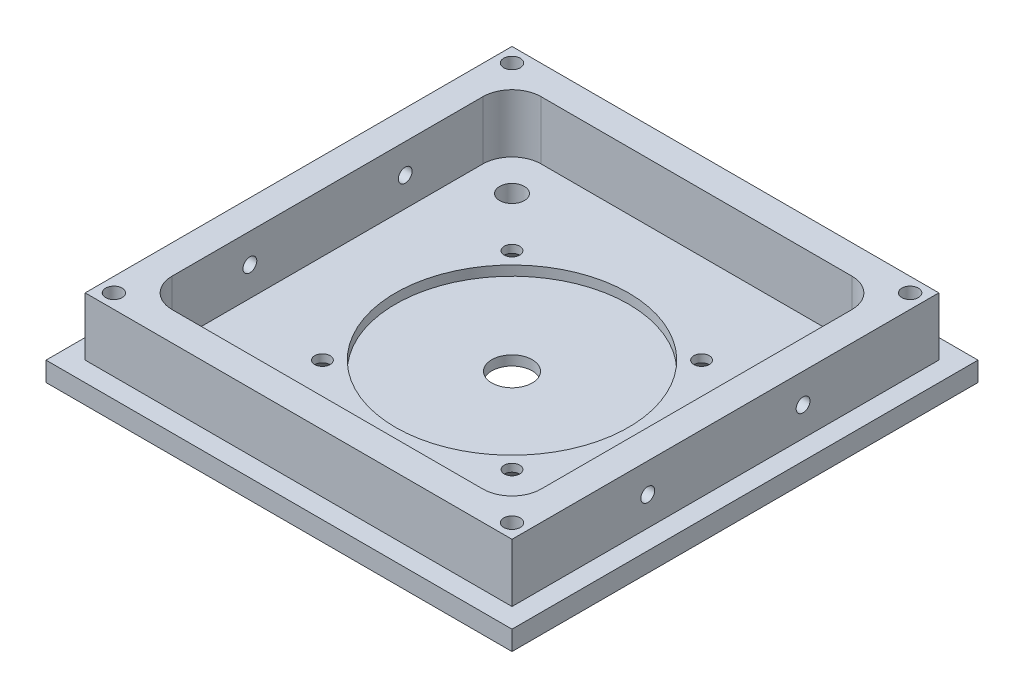
SolidWorks part; units mm, degrees
material "6061-T6 (SS)"
ref_plane "Front Plane" through (0, 0, 0) normal (0, 0, 1) x (1, 0, 0)
ref_plane "Top Plane" through (0, 0, 0) normal (0, 1, 0) x (1, 0, 0)
ref_plane "Right Plane" through (0, 0, 0) normal (1, 0, 0) x (0, 0, -1)
sketch "Sketch1" plane through (0, 0, 0) normal (0, 1, 0) x (1, 0, 0)
  line L1 (-38.1, -38.1) -> (38.1, -38.1)
  line L2 (-38.1, -38.1) -> (-38.1, 38.1)
  line L3 (-38.1, 38.1) -> (38.1, 38.1)
  line L4 (38.1, -38.1) -> (38.1, 38.1)
  line L5 (-38.1, -38.1) -> (38.1, 38.1) construction
  line L6 (-38.1, 38.1) -> (38.1, -38.1) construction
  point P0 (0, 0)
  dimension "D1" = 76.2
  dimension "D2" = 76.2
extrude "Boss-Extrude1" add sketch "Sketch1" along normal blind 3.175
sketch "Sketch2" plane through (0, 3.175, 0) normal (0, 1, 0) x (1, 0, 0)
  line L0 (-38.1, 38.1) -> (-38.1, -38.1) construction
  line L1 (34.8971, -34.8971) -> (-34.8971, -34.8971)
  line L2 (34.8971, -34.8971) -> (34.8971, 34.8971)
  line L3 (34.8971, 34.8971) -> (-34.8971, 34.8971)
  line L4 (-34.8971, -34.8971) -> (-34.8971, 34.8971)
  line L5 (34.8971, -34.8971) -> (-34.8971, 34.8971) construction
  line L6 (34.8971, 34.8971) -> (-34.8971, -34.8971) construction
  line L7 (30.1625, -30.1625) -> (-30.1625, -30.1625)
  line L8 (30.1625, -30.1625) -> (30.1625, 30.1625)
  line L9 (30.1625, 30.1625) -> (-30.1625, 30.1625)
  line L10 (-30.1625, -30.1625) -> (-30.1625, 30.1625)
  line L11 (30.1625, -30.1625) -> (-30.1625, 30.1625) construction
  line L12 (30.1625, 30.1625) -> (-30.1625, -30.1625) construction
  line L14 (38.1, 38.1) -> (-38.1, 38.1) construction
  point P0 (0, 0)
  point P6 (0, 0)
  dimension "D1" = 3.2029
  dimension "D2" = 3.2029
  dimension "D3" = 60.325
extrude "Boss-Extrude2" add sketch "Sketch2" along normal blind 9.525
fillet "Fillet1" radius 4.7625 4 edges at (-30.1625, 7.9375, 30.1625) (30.1625, 7.9375, 30.1625) (30.1625, 7.9375, -30.1625) (-30.1625, 7.9375, -30.1625)
sketch "Sketch3" plane through (0, 3.175, 0) normal (0, 1, 0) x (1, 0, 0)
  circle A0 centre (0, 0) radius 19.05
  dimension "D1" = 38.1
extrude "Cut-Extrude1" cut sketch "Sketch3" against normal blind 1.5875
sketch "Sketch4" plane through (0, 1.5875, 0) normal (0, 1, 0) x (1, 0, 0)
  circle A0 centre (0, 0) radius 3.302
  dimension "D1" = 6.604
extrude "Cut-Extrude2" cut sketch "Sketch4" against normal through all
sketch "Sketch5" plane through (0, 3.175, 0) normal (0, 1, 0) x (1, 0, 0)
  line L1 (15.5, -15.5) -> (-15.5, -15.5)
  line L2 (15.5, -15.5) -> (15.5, 15.5)
  line L3 (15.5, 15.5) -> (-15.5, 15.5)
  line L4 (-15.5, -15.5) -> (-15.5, 15.5)
  line L5 (15.5, -15.5) -> (-15.5, 15.5) construction
  line L6 (15.5, 15.5) -> (-15.5, -15.5) construction
  line L7 (23.5966, -23.5966) -> (-23.5966, -23.5966)
  line L8 (23.5966, -23.5966) -> (23.5966, 23.5966)
  line L9 (23.5966, 23.5966) -> (-23.5966, 23.5966)
  line L10 (-23.5966, -23.5966) -> (-23.5966, 23.5966)
  line L11 (23.5966, -23.5966) -> (-23.5966, 23.5966) construction
  line L12 (23.5966, 23.5966) -> (-23.5966, -23.5966) construction
  circle A0 centre (-15.5, 15.5) radius 1.2637
  circle A1 centre (15.5, 15.5) radius 1.2637
  circle A2 centre (15.5, -15.5) radius 1.2637
  circle A3 centre (-15.5, -15.5) radius 1.2637
  point P2 (0, 0)
  point P10 (0, 0)
  dimension "D2" = 2.5273
  dimension "D1" = 31
  dimension "D3" = 47.1932
hole_wizard "#39 (0.0995) Diameter Hole1" positions "Sketch7" profile "Sketch6" hole size "#39" standard "ANSI Inch" end condition through all
sketch "Sketch7" plane through (0, 3.175, 0) normal (0, 1, 0) x (1, 0, 0)
  point P0 (15.5, 15.5)
  point P3 (-15.5, 15.5)
  point P6 (-15.5, -15.5)
  point P9 (15.5, -15.5)
  point P12 (-23.5966, 23.5966)
  point P15 (23.5966, 23.5966)
  point P18 (23.5966, -23.5966)
  point P21 (-23.5966, -23.5966)
sketch "Sketch6" plane through (15.5, 3.175, -15.5) normal (1, 0, 0) x (0, 0, 1)
  line L0 (0, 0) -> (0, 3.175)
  line L1 (0, 3.175) -> (1.2636, 3.175)
  line L2 (1.2636, 3.175) -> (1.2636, 0)
  line L5 (1.2636, 0) -> (0, 0)
  line L11 (0, -6.35) -> (0, 107.95) construction
  dimension "Thru Hole Dia." = 2.5273
  dimension "Thru Hole Depth" = 3.175
hole_wizard "#10-32 Tapped Hole1" positions "Sketch17" profile "Sketch15" tap size "#10-32" standard "ANSI Inch" end condition through all
sketch "Sketch17" plane through (0, 3.175, 0) normal (0, 1, 0) x (1, 0, 0)
  point P0 (-23.5966, 23.5966)
  point P3 (23.5966, 23.5966)
  point P6 (23.5966, -23.5966)
  point P9 (-23.5966, -23.5966)
sketch "Sketch15" plane through (-23.5966, 3.175, -23.5966) normal (1, 0, 0) x (0, 0, 1)
  line L0 (0, 0) -> (0, 3.175)
  line L1 (0, 3.175) -> (2.0193, 3.175)
  line L2 (2.0193, 3.175) -> (2.0193, 0)
  line L5 (2.0193, 0) -> (0, 0)
  line L11 (0, -6.35) -> (0, 107.95) construction
  dimension "Thru Tap Drill Dia." = 4.0386
  dimension "Thru Tap Drill Depth" = 3.175
cosmetic thread "Hole Thread3" parameters "D2"=4.826
cosmetic thread "Hole Thread4" parameters "D2"=4.826
cosmetic thread "Hole Thread5" parameters "D2"=4.826
cosmetic thread "Hole Thread6" parameters "D2"=4.826
sketch "Sketch8" plane through (34.8971, 0, 0) normal (1, 0, 0) x (0, 0, -1)
  line L0 (-38.1, 3.175) -> (38.1, 3.175) construction
  point P0 (-12.7, 7.9375)
  dimension "D1" = 4.7625
  dimension "D2" = 12.7
hole_wizard "#4-40 Tapped Hole1" positions "Sketch10" profile "Sketch9" tap size "#4-40" standard "ANSI Inch"
sketch "Sketch10" plane through (34.8971, 0, 0) normal (1, 0, 0) x (0, 0, -1)
  point P0 (-12.7, 7.9375)
sketch "Sketch9" plane through (34.8971, 7.9375, 12.7) normal (0, 1, 0) x (0, 0, -1)
  line L0 (0, 0) -> (0, 7.2832)
  line L1 (0, 7.2832) -> (1.1303, 6.604)
  line L2 (1.1303, 6.604) -> (1.1303, 0)
  line L5 (1.1303, 0) -> (0, 0)
  line L10 (0, 7.2832) -> (-1.1303, 6.604) construction
  line L11 (0, -6.35) -> (0, 107.95) construction
  dimension "Tap Drill Dia." = 2.2606
  dimension "Tap Drill Depth" = 6.604
  dimension "Drill Angle" = 118
cosmetic thread "Hole Thread1" parameters "D1"=2.4486, "D2"=2.8448
mirror "Mirror1" about plane through (0, 0, 0) normal (0, 0, 1) of "#4-40 Tapped Hole1"
mirror "Mirror2" about plane through (0, 0, 0) normal (1, 0, 0) of "Mirror1"
chamfer "Chamfer1" distance 1.905 angle 41 4 edges at (-15.5, 0, -14.2363) (15.5, 0, -14.2364) (15.5, 0, 16.7636) (-15.5, 0, 16.7637) first distance on face at (-15.5, 0, -14.2363) first distance on face at (15.5, 0, -14.2364) first distance on face at (15.5, 0, 16.7636) first distance on face at (-15.5, 0, 16.7637)
sketch "Sketch11" plane through (0, 0, 0) normal (0, -1, 0) x (1, 0, 0)
  circle A0 centre (32.5501, -32.5501) radius 2.032
  dimension "D1" = 4.064
hole_wizard "#6-32 Tapped Hole1" positions "Sketch13" profile "Sketch12" tap size "#6-32" standard "ANSI Inch" end condition through all
sketch "Sketch13" plane through (0, 0, 0) normal (0, -1, 0) x (-1, 0, 0)
  point P0 (-32.5501, 32.5501)
sketch "Sketch12" plane through (32.5501, 0, -32.5501) normal (1, 0, 0) x (0, 0, -1)
  line L0 (0, 0) -> (0, 12.7)
  line L1 (0, 12.7) -> (1.3525, 12.7)
  line L2 (1.3525, 12.7) -> (1.3525, 0)
  line L5 (1.3525, 0) -> (0, 0)
  line L11 (0, -6.35) -> (0, 107.95) construction
  dimension "Thru Tap Drill Dia." = 2.7051
  dimension "Thru Tap Drill Depth" = 12.7
cosmetic thread "Hole Thread2" parameters "D2"=3.5052
pattern_circular "CirPattern1" count 4 over 360 about axis through (0, 0, 0) along (0, 1, 0) of "#6-32 Tapped Hole1"
equation "\"D2@Sketch2\"=\"D1@Sketch2\""
equation "\"D2@Sketch1\"=\"D1@Sketch1\""
